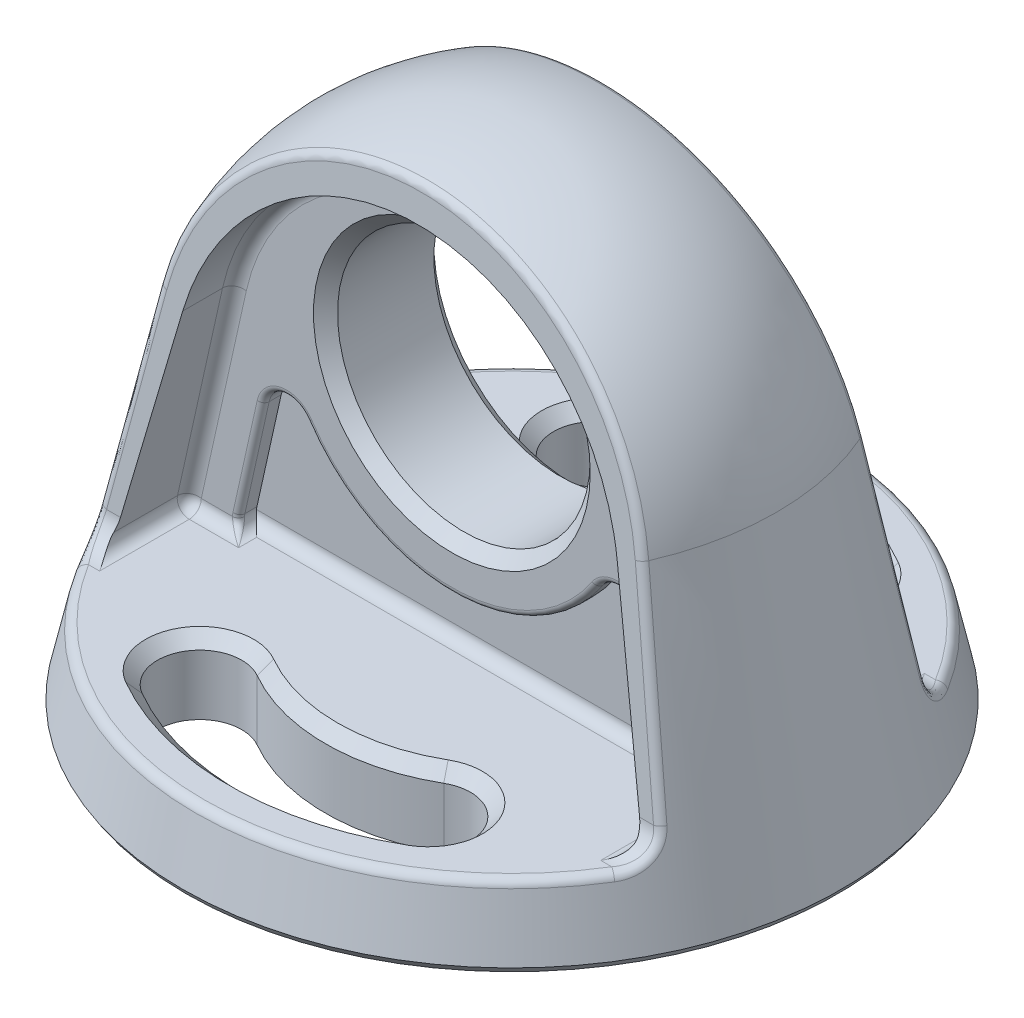
SolidWorks part; units mm, degrees
ref_plane "Front Plane" through (0, 0, 0) normal (0, 0, 1) x (1, 0, 0)
ref_plane "Top Plane" through (0, 0, 0) normal (0, 1, 0) x (1, 0, 0)
ref_plane "Right Plane" through (0, 0, 0) normal (1, 0, 0) x (0, 0, -1)
sketch "Sketch1" plane through (0, 0, 0) normal (0, 0, 1) x (1, 0, 0)
  line L0 (0, 0) -> (-55, 0)
  line L1 (0, 0) -> (0, 85)
  line L2 (-43.9259, 49.7731) -> (-55, 0)
  arc A0 (0, 85) -> (-43.9259, 49.7731) centre (0, 40) ccw
  dimension "D3" = 45
  dimension "D1" = 55
  dimension "D2" = 85
revolve "Revolve1" add sketch "Sketch1" angle 360 about L1
sketch "Sketch2" plane through (0, 0, 0) normal (1, 0, 0) x (0, 0, -1)
  line L0 (0, 85) -> (0, 0) construction
  line L1 (55, 0) -> (-55, 0)
  line L2 (-55, 0) -> (-52.3301, 12)
  line L3 (-43.9259, 49.7731) -> (-55, 0) construction
  line L4 (-52.3301, 12) -> (-22.4021, 12)
  line L5 (-22.4021, 12) -> (-15, 82.4264)
  line L6 (22.4021, 12) -> (15, 82.4264)
  line L7 (52.3301, 12) -> (22.4021, 12)
  line L8 (55, 0) -> (52.3301, 12)
  arc A0 (43.9259, 49.7731) -> (-43.9259, 49.7731) centre (0, 40) ccw construction
  arc A1 (15, 82.4264) -> (-15, 82.4264) centre (0, 40) ccw
  point P17 (-6.9837, 84.4548)
  dimension "D1" = 30
  dimension "D2" = 12
  dimension "D3" = 12
extrude "Cut-Extrude1" cut sketch "Sketch2" against normal through all both and the other way through all flip side to cut contours A1 L5 L4 L2 L1 L8 L7 L6
sketch "Sketch4" plane through (0, 0, 0) normal (0, 0, 1) x (1, 0, 0)
  line L3 (-44.1504, 11.9283) -> (44.1345, 12)
  line L4 (-47.2925, 12) -> (47.2925, 12) construction
  line L5 (47.1909, -1.7374) -> (36.1169, 48.0357)
  line L6 (-36.1169, 48.0357) -> (-47.1909, -1.7374)
  line L7 (44.1345, 12) -> (36.1169, 48.0357)
  line L8 (-36.1169, 48.0357) -> (-44.1504, 11.9283)
  line L9 (-44.1345, 12) -> (44.1345, 12)
  line L11 (-55, 0) -> (55, 0) construction
  line L12 (-55, 0) -> (55, 0)
  line L13 (0, 50) -> (0, 0) construction
  line L14 (-31.3633, 32.5653) -> (-35.9533, 11.935)
  line L15 (31.3633, 32.5653) -> (35.9533, 11.935)
  circle A3 centre (0, 50) radius 21
  arc A4 (36.1169, 48.0357) -> (-36.1169, 48.0357) centre (0, 40) ccw
  arc A5 (36.1169, 48.0357) -> (-36.1169, 48.0357) centre (0, 40) ccw
  arc A6 (-24.1304, 33.9151) -> (24.1304, 33.9151) centre (0, 50) ccw
  arc A7 (31.3633, 32.5653) -> (24.1304, 33.9151) centre (27.4588, 31.6965) ccw
  arc A8 (-24.1304, 33.9151) -> (-31.3633, 32.5653) centre (-27.4588, 31.6965) ccw
  point P15 (0, 0)
  point P16 (0, 0)
  point P23 (0, 0)
  point P25 (28.5793, 45.0781)
  point P28 (-28.5793, 45.0781)
  dimension "D4" = 42
  dimension "D6" = 29
  dimension "D7" = 4
  dimension "D2" = 44.1504
  dimension "D3" = 50
  dimension "D5" = 8
  dimension "D1" = 8
extrude "Cut-Extrude5" cut sketch "Sketch4" against normal through all both and the other way through all contours A3
extrude "Cut-Extrude8" cut sketch "Sketch4<9>" against normal through all from offset 10 contours A3 A6 A7 L15 L9 L7 A5 L8 L14 A8 region at (-39.0556, 29.7798, 0) offset against normal yes
sketch "Sketch4<9>" plane through (0, 0, 0) normal (0, 0, 1) x (1, 0, 0) same geometry as "Sketch4"
extrude "Cut-Extrude9" cut sketch "Sketch4<10>" along normal through all from offset 10 contours A3 A6 A7 L15 L9 L7 A5 L8 L14 A8 region at (-39.0556, 29.7798, 0)
sketch "Sketch4<10>" plane through (0, 0, 0) normal (0, 0, 1) x (1, 0, 0) same geometry as "Sketch4"
extrude "Cut-Extrude11" cut sketch "Sketch4<12>" along normal through all from offset 7 contours L13 A6 A8 L14 L9 | A6 L13 L9 L15 A7 region at (-20.0416, 20.3892, 0) region at (20.0416, 20.3892, 0)
sketch "Sketch4<12>" plane through (0, 0, 0) normal (0, 0, 1) x (1, 0, 0) same geometry as "Sketch4"
extrude "Cut-Extrude19" cut sketch "Sketch4<18>" against normal through all from offset 7 contours A6 L13 L9 L15 A7 | L13 A6 A8 L14 L9 region at (-20.0416, 20.3892, 0) region at (20.0416, 20.3892, 0) offset against normal yes
sketch "Sketch4<18>" plane through (0, 0, 0) normal (0, 0, 1) x (1, 0, 0) same geometry as "Sketch4"
sketch "Sketch6" plane through (0, 12, 0) normal (0, 1, 0) x (1, 0, 0)
  line L0 (19, 32.909) -> (0, 0) construction
  line L1 (0, 38) -> (0, 0)
  line L2 (-19, 32.909) -> (0, 0) construction
  line L3 (-38, 0) -> (0, 0) construction
  circle A0 centre (0, 0) radius 38 construction
  arc A1 (19, 32.909) -> (-19, 32.909) centre (0, 0) ccw construction
  arc A6 (22.5, 38.9711) -> (-22.5, 38.9711) centre (0, 0) ccw
  arc A7 (15.5, 26.8468) -> (-15.5, 26.8468) centre (0, 0) ccw
  arc A8 (15.5, 26.8468) -> (22.5, 38.9711) centre (19, 32.909) ccw
  arc A9 (-22.5, 38.9711) -> (-15.5, 26.8468) centre (-19, 32.909) ccw
  arc A10 (19, -32.909) -> (-19, -32.909) centre (0, 0) cw construction
  arc A11 (22.5, -38.9711) -> (-22.5, -38.9711) centre (0, 0) cw
  arc A12 (15.5, -26.8468) -> (-15.5, -26.8468) centre (0, 0) cw
  arc A13 (15.5, -26.8468) -> (22.5, -38.9711) centre (19, -32.909) cw
  arc A14 (-22.5, -38.9711) -> (-15.5, -26.8468) centre (-19, -32.909) cw
  point P5 (0, 38)
  point P17 (0, -38)
  dimension "D1" = 76
  dimension "D2" = 60
  dimension "D4" = 7
  dimension "D3" = 30
extrude "Cut-Extrude20" cut sketch "Sketch6" against normal through all contours A14 A11 A13 A12 | A6 A9 A7 A8 region at (0, 12, 35.5559)
chamfer "Chamfer1" distance 2 angle 45 9 edges at (0, 12, -31) (25.0622, 12, -29.409) (-25.0622, 12, -29.409) (0, 12, -45) (0, 12, 31) (25.0622, 12, 29.409) (-25.0622, 12, 29.409) (0, 12, 45) (21, 50, 10)
chamfer "Chamfer2" distance 1 angle 45 1 edges at (0, 0, -55) first distance on face at (0, 0, -55)
fillet "Fillet1" radius 5 4 edges at (45.7135, 12, -22.4021) (-45.7135, 12, -22.4021) (45.7135, 12, 22.4021) (-45.7135, 12, 22.4021)
fillet "Fillet2" radius 2 20 edges at (-40.1257, 30.0178, -10) (0, 77, -10) (-40.1257, 30.0178, 10) (0, 77, 10) (-44.1345, 12, -18.4521) (-40.0367, 12, -10) (-35.9389, 12, -8.5) (44.1345, 12, -18.4521) (40.0367, 12, -10) (35.9389, 12, -8.5) (0, 12, -7) (40.1257, 30.0178, -10) (35.9389, 12, 8.5) (-35.9389, 12, 8.5) (-40.0367, 12, 10) (40.0367, 12, 10) (-44.1345, 12, 18.4521) (44.1345, 12, 18.4521) (0, 12, 7) (40.1257, 30.0178, 10)
fillet "Fillet3" radius 1.5 12 edges at (46.5228, 13.7714, 23.0862) (0, 82.4264, 15) (-46.3729, 13.1821, 23.6756) (46.3729, 13.1821, -23.6756) (0, 82.4264, -15) (-46.5228, 13.7714, -23.0862) (0, 12, 52.3301) (0, 12, -52.3301)
fillet "Fillet4" radius 1 18 edges at (-34.8592, 12.5858, -10.5858) (-35.433, 14.2185, -10) (-33.3803, 23.4998, -10) (-28.1926, 35.6286, -10) (34.8592, 12.5858, -10.5858) (35.433, 14.2185, -10) (33.3803, 23.4998, -10) (28.1926, 35.6286, -10) (-34.8592, 12.5858, 10.5858) (-35.433, 14.2185, 10) (-33.3803, 23.4998, 10) (-28.1926, 35.6286, 10) (34.8592, 12.5858, 10.5858) (35.433, 14.2185, 10) (33.3803, 23.4998, 10) (28.1926, 35.6286, 10) (0, 21, -10) (0, 21, 10)
chamfer "Chamfer3" distance 2 angle 45 1 edges at (21, 50, -10)
